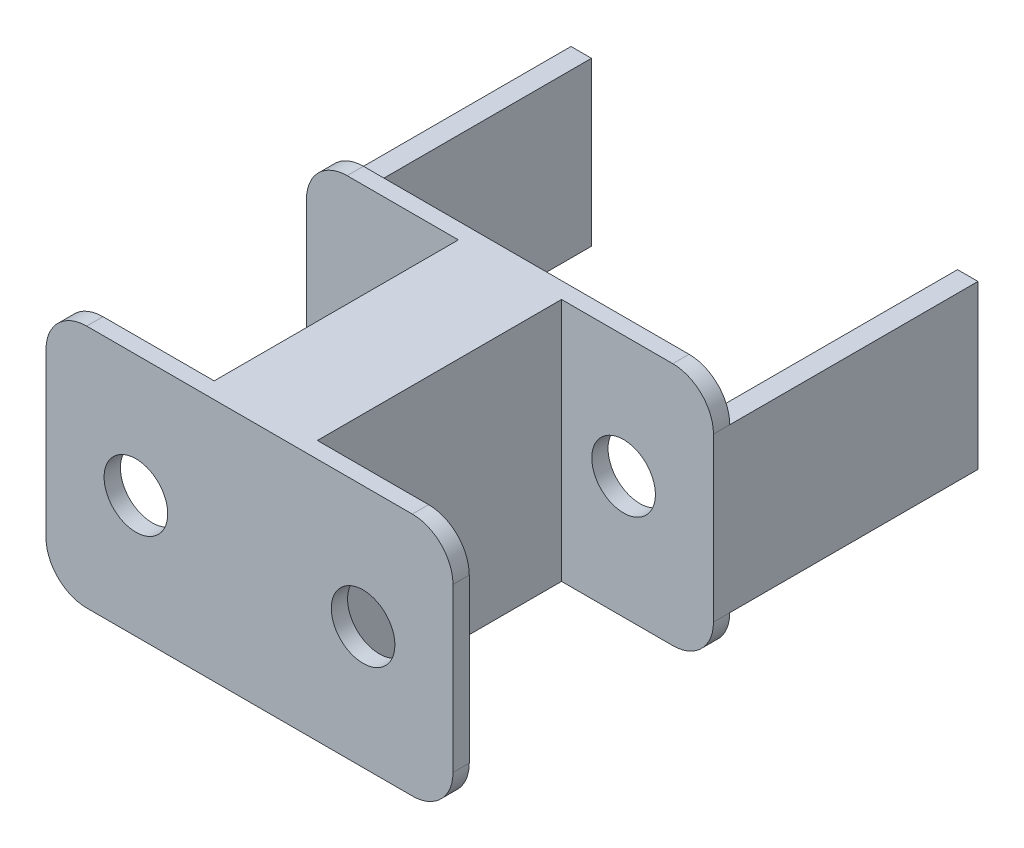
SolidWorks part; units mm, degrees
ref_plane "Спереди" through (0, 0, 0) normal (0, 0, 1) x (1, 0, 0)
ref_plane "Сверху" through (0, 0, 0) normal (0, 1, 0) x (1, 0, 0)
ref_plane "Справа" through (0, 0, 0) normal (1, 0, 0) x (0, 0, -1)
sketch "Эскиз1" plane through (0, 0, 0) normal (0, 0, 1) x (1, 0, 0)
  line L1 (-90, 60) -> (-10, 60)
  line L2 (-100, 50) -> (-100, 10)
  line L3 (-90, 0) -> (-10, 0)
  line L4 (0, 50) -> (0, 10)
  arc A0 (-100, 10) -> (-90, 0) centre (-90, 10) ccw
  arc A1 (-10, 0) -> (0, 10) centre (-10, 10) ccw
  arc A2 (0, 50) -> (-10, 60) centre (-10, 50) ccw
  arc A3 (-90, 60) -> (-100, 50) centre (-90, 50) ccw
  point P10 (0, 0)
  dimension "D1" = 10
extrude "Бобышка-Вытянуть1" add sketch "Эскиз1" along normal blind 68
sketch "Эскиз2" plane through (0, 60, 0) normal (0, 1, 0) x (1, 0, 0)
  line L0 (-37.3234, -4) -> (-37.3234, -64)
  line L1 (-111.8917, -4) -> (-62.6766, -4)
  line L2 (-111.8917, -4) -> (-111.8917, -64)
  line L3 (-111.8917, -64) -> (-62.6766, -64)
  line L4 (-62.6766, -4) -> (-62.6766, -64)
  line L5 (11.8917, -64) -> (-37.3234, -64)
  line L7 (11.8917, -4) -> (11.8917, -64)
  line L11 (11.8917, -4) -> (-37.3234, -4)
extrude "Вырез-Вытянуть1" cut sketch "Эскиз2" against normal up to surface (60 mm away) up to face at (-50, 0, 34)
sketch "Эскиз3" plane through (0, 0, 0) normal (0, 0, -1) x (-1, 0, 0)
  circle A0 centre (77.9118, 30) radius 7.8153
  circle A1 centre (22.0882, 30) radius 7.8153
extrude "Вырез-Вытянуть2" cut sketch "Эскиз3" against normal up to surface (68 mm away) contours A1 up to face at (-50, 30, 68)
extrude "Вырез-Вытянуть3" cut sketch "Эскиз3<4>" against normal up to surface (68 mm away) up to face at (-14.273, 30, 68)
sketch "Эскиз3<4>" plane through (0, 0, 0) normal (0, 0, -1) x (-1, 0, 0) same geometry as "Эскиз3"
sketch "Эскиз5" plane through (0, 0, 0) normal (0, 0, -1) x (-1, 0, 0)
  line L2 (0, 50) -> (5.0293, 50)
  line L3 (0, 50) -> (0, 10)
  line L4 (0, 10) -> (5.0293, 10)
  line L5 (5.0293, 50) -> (5.0293, 10)
  line L8 (94.9707, 50) -> (94.9707, 10)
  line L9 (100, 10) -> (94.9707, 10)
  line L10 (100, 50) -> (100, 10)
  line L11 (100, 50) -> (94.9707, 50)
extrude "Бобышка-Вытянуть2" add sketch "Эскиз5" along normal blind 61
